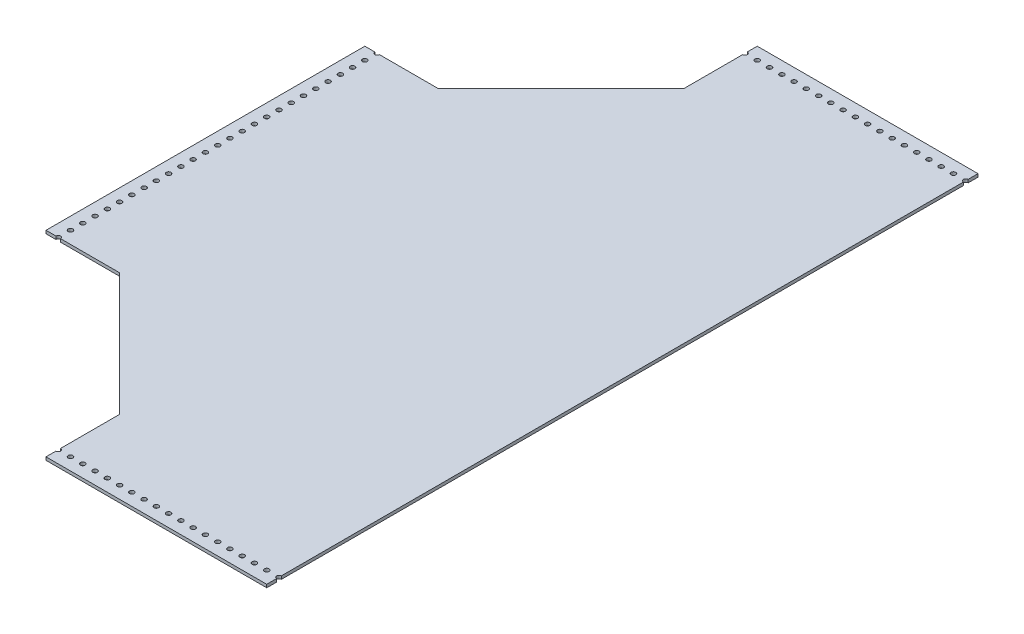
SolidWorks part; units mm, degrees
material "ABS PC"
ref_plane "Front Plane" through (0, 0, 0) normal (0, 0, 1) x (1, 0, 0)
ref_plane "Top Plane" through (0, 0, 0) normal (0, 1, 0) x (1, 0, 0)
ref_plane "Right Plane" through (0, 0, 0) normal (1, 0, 0) x (0, 0, -1)
sketch "Sketch1" plane through (0, 0, 0) normal (0, 1, 0) x (1, 0, 0)
  line L1 (-317.5, -368.3) -> (317.5, -368.3)
  line L2 (-317.5, -368.3) -> (-317.5, 368.3)
  line L3 (-317.5, 368.3) -> (317.5, 368.3)
  line L4 (317.5, -368.3) -> (317.5, 368.3)
  line L5 (-317.5, -368.3) -> (317.5, 368.3) construction
  line L6 (-317.5, 368.3) -> (317.5, -368.3) construction
  point P0 (0, 0)
  dimension "D1" = 635
  dimension "D2" = 736.6
extrude "Base" add sketch "Sketch1" along normal blind 3.175
sketch "Sketch3" plane through (0, 3.175, 0) normal (0, 1, 0) x (1, 0, 0)
  line L0 (317.5, -368.3) -> (317.5, 368.3) construction
  line L6 (317.5, 368.3) -> (-317.5, 368.3) construction
  line L7 (-317.5, 368.3) -> (-317.5, -368.3) construction
  circle A0 centre (-304.8, 355.6) radius 2.413
  circle A1 centre (304.8, 355.6) radius 2.413
  dimension "D1" = 4.826
  dimension "D2" = 4.826
  dimension "D3" = 12.7
  dimension "D4" = 12.7
  dimension "D5" = 12.7
  dimension "D6" = 12.7
extrude "Initial Pattern Hole" cut sketch "Sketch3" against normal through all
pattern_linear "Hole Pattern 1" count 58 spacing 12.7 along (0, 0, 1) of "Initial Pattern Hole"
pattern_linear "Hole Pattern 2" count 48 spacing 12.7 along (1, 0, 0) of face at (-304.8, 0, 358.013) of face at (-304.8, 0, -353.187)
sketch "Sketch2" plane through (0, 0, 0) normal (0, -1, 0) x (-1, 0, 0)
  line L16 (-317.5, 368.3) -> (-317.5, 184.15)
  line L17 (-317.5, -368.3) -> (-317.5, 368.3) construction
  line L18 (-317.5, 184.15) -> (-292.1004, 184.15)
  line L19 (-292.1004, 184.15) -> (-133.35, 342.9004)
  line L20 (-133.35, 342.9004) -> (-133.35, 368.3)
  line L21 (-317.5, 368.3) -> (317.5, 368.3) construction
  line L22 (-133.35, 368.3) -> (-317.5, 368.3)
  line L23 (133.35, 368.3) -> (317.5, 368.3)
  line L24 (317.5, 368.3) -> (317.5, 184.15)
  line L25 (317.5, 368.3) -> (317.5, -368.3) construction
  line L26 (317.5, 184.15) -> (292.1004, 184.15)
  line L27 (292.1004, 184.15) -> (133.35, 342.9004)
  line L28 (133.35, 342.9004) -> (133.35, 368.3)
  line L29 (317.5, -368.3) -> (317.5, -184.15)
  line L30 (317.5, -184.15) -> (292.1004, -184.15)
  line L31 (292.1004, -184.15) -> (133.35, -342.9004)
  line L32 (133.35, -342.9004) -> (133.35, -368.3)
  line L33 (317.5, -368.3) -> (307.213, -368.3) construction
  line L34 (133.35, -368.3) -> (317.5, -368.3)
  line L35 (-133.35, -368.3) -> (-133.35, -342.9004)
  line L36 (-133.35, -342.9004) -> (-292.1004, -184.15)
  line L37 (-292.1004, -184.15) -> (-317.5, -184.15)
  line L38 (-317.5, -184.15) -> (-317.5, -368.3)
  line L39 (-317.5, -368.3) -> (-133.35, -368.3)
  dimension "D1" = 184.15
extrude "Module Cutout" [suppressed] cut sketch "Sketch2" against normal through all
sketch "Sketch4" plane through (0, 3.175, 0) normal (0, 1, 0) x (1, 0, 0)
  line L24 (-317.5, 165.1) -> (-241.3, 165.1)
  line L25 (-317.5, 368.3) -> (-317.5, -368.3) construction
  line L26 (-241.3, 165.1) -> (-114.3, 292.1)
  line L27 (-114.3, 292.1) -> (-114.3, 368.3)
  line L28 (317.5, 368.3) -> (-317.5, 368.3) construction
  line L29 (-317.5, -368.3) -> (-114.3, -368.3)
  line L30 (-114.3, -368.3) -> (-114.3, -292.1)
  line L31 (-114.3, -292.1) -> (-241.3, -165.1)
  line L32 (-241.3, -165.1) -> (-317.5, -165.1)
  line L33 (-317.5, -165.1) -> (-317.5, -368.3)
  line L34 (-317.5, 165.1) -> (-317.5, 368.3)
  line L35 (-317.5, 368.3) -> (-114.3, 368.3)
  line L36 (317.5, 368.3) -> (114.3, 368.3)
  line L37 (114.3, 368.3) -> (114.3, -368.3)
  line L39 (317.5, 152.4) -> (317.5, 260.35) construction
  line L40 (317.5, -368.3) -> (317.5, 368.3)
  line L44 (-302.387, -368.3) -> (302.387, -368.3) construction
  line L45 (114.3, -368.3) -> (317.5, -368.3)
  dimension "D1" = 76.2
  dimension "D2" = 76.2
  dimension "D3" = 203.2
  dimension "D4" = 203.2
  dimension "D6" = 203.2
extrude "Top Module Cutout" cut sketch "Sketch4" against normal through all
